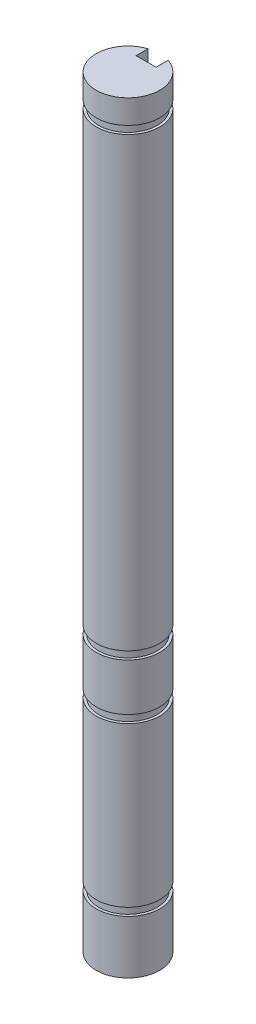
SolidWorks part; units mm, degrees
note: The reader was unsure of these and kept them because the rebuilt part matched: shared geometry of "Sketch3<6>", "Sketch3<7>".
material "1023 Carbon Steel Sheet (SS)"
ref_plane "Front Plane" through (0, 0, 0) normal (0, 0, 1) x (1, 0, 0)
ref_plane "Top Plane" through (0, 0, 0) normal (0, 1, 0) x (1, 0, 0)
ref_plane "Right Plane" through (0, 0, 0) normal (1, 0, 0) x (0, 0, -1)
sketch "Sketch1" plane through (0, 0, 0) normal (0, 1, 0) x (1, 0, 0)
  line L0 (-1, 3.0134) -> (-1, 1.8134)
  line L1 (-1, 1.8134) -> (1, 1.8134)
  line L2 (1, 1.8134) -> (1, 3.0134)
  arc A0 (-1, 3.0134) -> (1, 3.0134) centre (0, 0) ccw
  point P5 (0, 1.8134)
  dimension "D1" = 6.35
  dimension "D2" = 2
  dimension "D3" = 1.2
extrude "Boss-Extrude1" add sketch "Sketch1" along normal blind 76.2
sketch "Sketch2" plane through (0, 76.2, 0) normal (0, 1, 0) x (1, 0, 0)
  circle A0 centre (0, 0) radius 2.921
  circle A1 centre (0, 0) radius 3.175
  arc A2 (-1, 3.0134) -> (1, 3.0134) centre (0, 0) ccw construction
  dimension "D1" = 0.254
extrude "Cut-Extrude1" cut sketch "Sketch2" along normal blind 0.7874 from offset 3.175 offset against normal yes
sketch "Sketch3" plane through (0, 0, 0) normal (0, -1, 0) x (0, 0, -1)
  circle A0 centre (0, 0) radius 2.921
  circle A1 centre (0, 0) radius 3.175
  dimension "D1" = 0.254
extrude "Cut-Extrude2" cut sketch "Sketch3" along normal blind 0.7874 from offset 28.321 offset against normal yes
extrude "Cut-Extrude3" cut sketch "Sketch3<6>" along normal blind 0.7874 from offset 22.8092 offset against normal yes
sketch "Sketch3<6>" plane through (0, 0, 0) normal (0, -1, 0) x (0, 0, -1) same geometry as "Sketch3"
extrude "Cut-Extrude4" cut sketch "Sketch3<7>" along normal blind 0.7874 from offset 6.1214
sketch "Sketch3<7>" plane through (0, 0, 0) normal (0, -1, 0) x (0, 0, -1) same geometry as "Sketch3"
